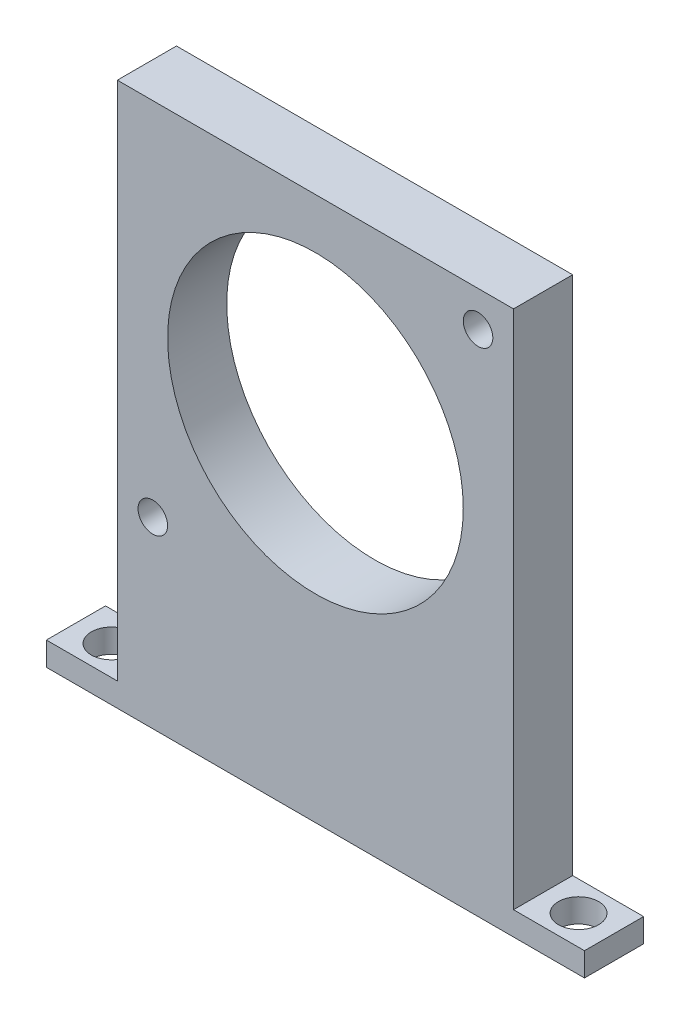
SolidWorks part; units mm, degrees
ref_plane "Front Plane" through (0, 0, 0) normal (0, 0, 1) x (1, 0, 0)
ref_plane "Top Plane" through (0, 0, 0) normal (0, 1, 0) x (1, 0, 0)
ref_plane "Right Plane" through (0, 0, 0) normal (1, 0, 0) x (0, 0, -1)
sketch "Sketch1" plane through (0, 0, 0) normal (0, 0, 1) x (1, 0, 0)
  line L0 (22.75, 0) -> (22.75, 46) construction
  line L1 (0, 0) -> (45.5, 0)
  line L2 (0, 0) -> (0, 2)
  line L3 (0, 2) -> (6, 2)
  line L4 (45.5, 0) -> (45.5, 2)
  line L5 (39.5, 2) -> (39.5, 46)
  line L6 (39.5, 46) -> (6, 46)
  line L7 (6, 2) -> (6, 46)
  line L8 (39.5, 2) -> (45.5, 2)
  dimension "D1" = 44
  dimension "D2" = 33.5
  dimension "D3" = 2
  dimension "D4" = 6
extrude "Boss-Extrude1" add sketch "Sketch1" along normal blind 5 contours L7 L6 L5 L8 L4 L1 L2 L3
hole_wizard "M3x0.5 Tapped Hole1" positions "3DSketch1" profile "Sketch2" tap size "M3x0.5" standard "ANSI Metric" end condition through all
sketch3d "3DSketch1"
  line L0 (39.5, 2, 5) -> (39.5, 46, 5) construction
  line L1 (39.5, 46, 5) -> (6, 46, 5) construction
  line L4 (6, 2, 5) -> (6, 46, 5) construction
  point P0 (36.5, 43, 5)
  point P2 (9, 15.5, 5)
  dimension "D1" = 3
  dimension "D2" = 3
  dimension "D3" = 30.5
  dimension "D4" = 3
sketch "Sketch2" plane through (36.5, 43, 5) normal (1, 0, 0) x (0, -1, 0)
  line L0 (0, 0) -> (0, 5)
  line L1 (0, 5) -> (1.25, 5)
  line L2 (1.25, 5) -> (1.25, 0)
  line L5 (1.25, 0) -> (0, 0)
  line L11 (0, -6.35) -> (0, 107.95) construction
  dimension "Thread Major Dia." = 2.5
  dimension "Thru Tap Drill Depth" = 5
hole_wizard "M3 Clearance Hole2" positions "3DSketch2" profile "Sketch5" hole size "M3" standard "ANSI Metric" end condition through all
sketch3d "3DSketch2"
  line L0 (39.5, 2, 5) -> (45.5, 2, 5) construction
  line L1 (0, 2, 5) -> (6, 2, 5) construction
  point P0 (42.5, 2, 2.5)
  point P2 (3, 2, 2.5)
  point P8 (42.5, 2, 5)
  point P11 (3, 2, 5)
  dimension "D1" = 2.5
sketch "Sketch5" plane through (42.5, 2, 2.5) normal (1, 0, 0) x (0, 0, 1)
  line L0 (0, 0) -> (0, 2)
  line L1 (0, 2) -> (1.7, 2)
  line L2 (1.7, 2) -> (1.7, 0)
  line L5 (1.7, 0) -> (0, 0)
  line L11 (0, -6.35) -> (0, 107.95) construction
  dimension "Thru Hole Dia." = 3.4
  dimension "Thru Hole Depth" = 2
hole_wizard "Ø25.0mm Dowel Hole1" positions "Sketch8" profile "Sketch7" hole size "Ø25.0" standard "ANSI Metric" end condition through all
sketch "Sketch8" plane through (0, 0, 5) normal (0, 0, 1) x (1, 0, 0)
  line L0 (9, 15.5) -> (36.5, 43) construction
  point P0 (22.75, 29.25)
  point P9 (0, 0)
  point P10 (22.75, 29.25)
sketch "Sketch7" plane through (22.75, 29.25, 5) normal (1, 0, 0) x (0, -1, 0)
  line L0 (0, 0) -> (0, 5)
  line L1 (0, 5) -> (12.5, 5)
  line L2 (12.5, 5) -> (12.5, 0)
  line L5 (12.5, 0) -> (0, 0)
  line L11 (0, -6.35) -> (0, 107.95) construction
  dimension "Thru Hole Dia." = 25
  dimension "Thru Hole Depth" = 5
